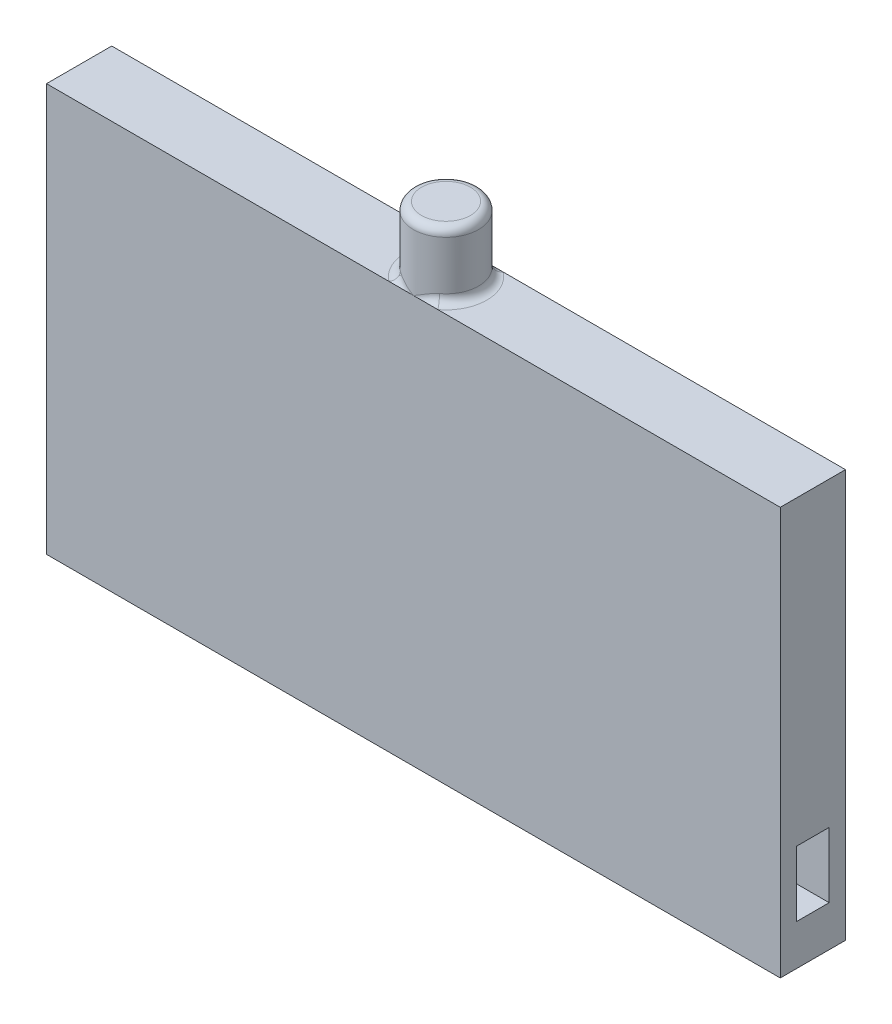
SolidWorks part; units mm, degrees
ref_plane "Front Plane" through (0, 0, 0) normal (0, 0, 1) x (1, 0, 0)
ref_plane "Top Plane" through (0, 0, 0) normal (0, 1, 0) x (1, 0, 0)
ref_plane "Right Plane" through (0, 0, 0) normal (1, 0, 0) x (0, 0, -1)
sketch "Sketch1" plane through (0, 0, 0) normal (0, 1, 0) x (1, 0, 0)
  line L1 (-9.906, 13.7078) -> (12.954, 13.7078)
  line L2 (-9.906, 13.7078) -> (-9.906, 15.7398)
  line L3 (-9.906, 15.7398) -> (12.954, 15.7398)
  line L4 (12.954, 13.7078) -> (12.954, 15.7398)
  dimension "D1" = 22.86
  dimension "D2" = 2.032
extrude "Boss-Extrude1" add sketch "Sketch1" along normal blind 12.7
sketch "Sketch2" plane through (0, 12.7, 0) normal (0, 1, 0) x (1, 0, 0)
  line L0 (12.954, 13.7078) -> (12.954, 15.7398) construction
  line L1 (-9.906, 13.7078) -> (12.954, 13.7078) construction
  circle A0 centre (1.524, 14.7238) radius 1.016
  dimension "D1" = 2.032
  dimension "D2" = 11.43
  dimension "D3" = 1.016
extrude "Boss-Extrude2" add sketch "Sketch2" along normal blind 2.032
fillet "Fillet1" radius 0.254 1 edges at (1.524, 14.732, -13.7078)
fillet "Fillet2" radius 0.254 2 edges at (0.508, 12.7, -14.7238) (2.54, 12.7, -14.7238)
sketch "Sketch3" plane through (12.954, 0, 0) normal (1, 0, 0) x (0, 0, -1)
  line L1 (14.2158, 1.27) -> (15.2318, 1.27)
  line L2 (14.2158, 1.27) -> (14.2158, 3.302)
  line L3 (14.2158, 3.302) -> (15.2318, 3.302)
  line L4 (15.2318, 1.27) -> (15.2318, 3.302)
  line L6 (15.7398, 12.7) -> (15.7398, 0) construction
  line L7 (13.7078, 12.7) -> (13.7078, 0) construction
  line L8 (13.7078, 0) -> (15.7398, 0) construction
  dimension "D1" = 0.508
  dimension "D2" = 0.508
  dimension "D3" = 2.032
  dimension "D4" = 1.27
extrude "Cut-Extrude1" cut sketch "Sketch3" against normal blind 2.54
